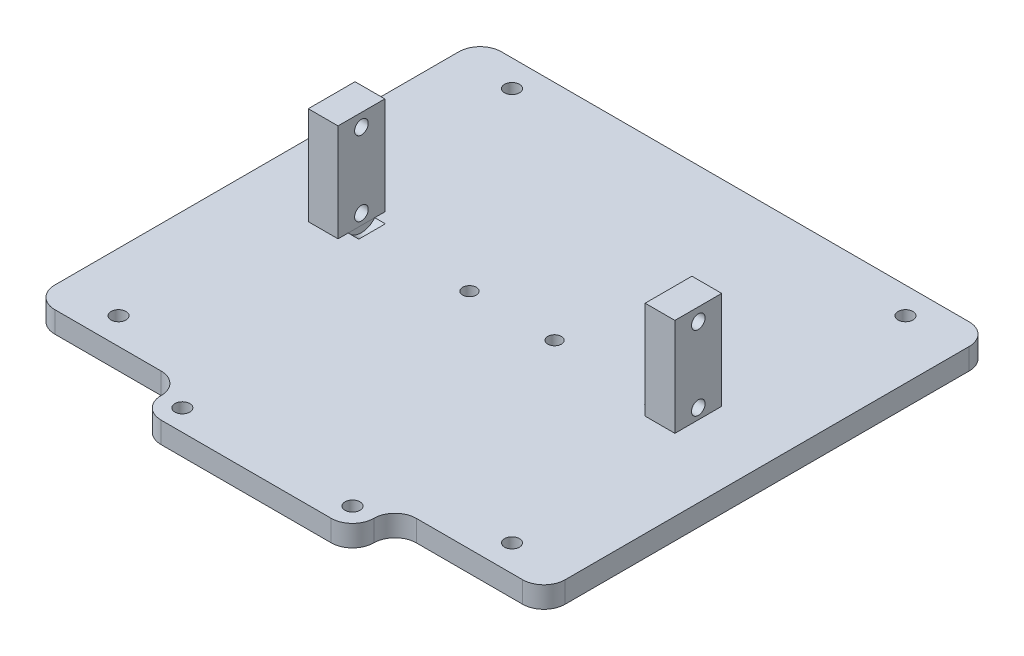
SolidWorks part; units mm, degrees
ref_plane "정면" through (0, 0, 0) normal (0, 0, 1) x (1, 0, 0)
ref_plane "윗면" through (0, 0, 0) normal (0, 1, 0) x (1, 0, 0)
ref_plane "우측면" through (0, 0, 0) normal (1, 0, 0) x (0, 0, -1)
sketch "스케치1" plane through (0, 0, 0) normal (0, 1, 0) x (1, 0, 0)
  line L0 (-25, -52.5) -> (-60, -52.5)
  line L1 (60, 52.5) -> (-60, 52.5)
  line L2 (60, 52.5) -> (60, -52.5)
  line L3 (60, -52.5) -> (25, -52.5)
  line L4 (-60, 52.5) -> (-60, -52.5)
  line L5 (60, 52.5) -> (-60, -52.5) construction
  line L6 (60, -52.5) -> (-60, 52.5) construction
  line L7 (25, -62.5) -> (-25, -62.5)
  line L8 (25, -62.5) -> (25, -52.5)
  line L10 (-25, -62.5) -> (-25, -52.5)
  line L11 (25, -62.5) -> (-25, -52.5) construction
  line L12 (25, -52.5) -> (-25, -62.5) construction
  point P0 (0, 0)
  point P6 (0, -57.5)
  dimension "D1" = 120
  dimension "D2" = 105
  dimension "D3" = 50
  dimension "D4" = 10
extrude "보스-돌출1" add sketch "스케치1" along normal blind 5
fillet "필렛1" radius 5 8 edges at (60, 2.5, -52.5) (60, 2.5, 52.5) (-60, 2.5, -52.5) (-60, 2.5, 52.5) (-25, 2.5, 52.5) (25, 2.5, 52.5) (25, 2.5, 62.5) (-25, 2.5, 62.5)
sketch "스케치2" plane through (0, 5, 0) normal (0, 1, 0) x (1, 0, 0)
  line L0 (-43.1, 29.5) -> (-43.1, -5.3) construction
  line L1 (-36.1, -4.8) -> (-43.1, -4.8)
  line L2 (-36.1, -4.8) -> (-36.1, 6.2)
  line L3 (-36.1, 6.2) -> (-43.1, 6.2)
  line L4 (-43.1, -4.8) -> (-43.1, 6.2)
  line L5 (-61.9, -0.8) -> (-43.1, -0.8) construction
  line L6 (-43.1, 2.2) -> (-61.9, 2.2) construction
  dimension "D1" = 7
  dimension "D2" = 4
  dimension "D3" = 4
extrude "보스-돌출2" add sketch "스케치2" along normal blind 23 separate body
sketch "스케치3" plane through (-36.1, 0, 0) normal (1, 0, 0) x (0, 0, -1)
  circle A0 centre (0.7, 7.5) radius 1.5 construction
  circle A1 centre (0.7, 25) radius 1.5 construction
  circle A2 centre (0.7, 25) radius 1.6
  circle A3 centre (0.7, 7.5) radius 1.6
  circle A4 centre (0.7, 7.5) radius 1.5 construction
  circle A5 centre (0.7, 25) radius 1.5 construction
  dimension "D1" = 3.2
  dimension "D2" = 3.2
extrude "컷-돌출1" cut sketch "스케치3" against normal through all
mirror "대칭 복사1" about plane through (0, 0, 0) normal (1, 0, 0) of bodies 103
sketch "스케치5" plane through (0, 5, 0) normal (0, 1, 0) x (1, 0, 0)
  circle A0 centre (-46.25, -46.25) radius 1.75 construction
  circle A1 centre (-46.25, 46.25) radius 1.75 construction
  circle A2 centre (46.25, 46.25) radius 1.75 construction
  circle A3 centre (46.25, -46.25) radius 1.75 construction
  circle A4 centre (-46.25, -46.25) radius 1.75
  circle A5 centre (-46.25, 46.25) radius 1.75
  circle A6 centre (46.25, 46.25) radius 1.75
  circle A7 centre (46.25, -46.25) radius 1.75
extrude "컷-돌출3" cut sketch "스케치5" against normal through all
sketch "스케치6" plane through (0, 5, 0) normal (0, 1, 0) x (1, 0, 0)
  circle A0 centre (20, -57.5) radius 1.75 construction
  circle A1 centre (-20, -57.5) radius 1.75 construction
  circle A2 centre (20, -57.5) radius 1.75
  circle A3 centre (-20, -57.5) radius 1.75
extrude "컷-돌출4" cut sketch "스케치6" against normal through all
sketch "Sketch2" plane through (36.1, 0, 0) normal (-1, 0, 0) x (0, 0, 1)
  circle A0 centre (-0.7, 7.5) radius 4
  dimension "D1" = 8
extrude "Cut-Extrude1" cut sketch "Sketch2" along normal blind 2.5
sketch "Sketch3" plane through (-36.1, 0, 0) normal (1, 0, 0) x (0, 0, -1)
  circle A0 centre (0.7, 7.5) radius 4
  dimension "D1" = 8
extrude "Cut-Extrude2" cut sketch "Sketch3" along normal blind 2.5
sketch "Sketch4" plane through (0, 5, 0) normal (0, 1, 0) x (1, 0, 0)
  circle A0 centre (10, 0) radius 1.5 construction
  circle A1 centre (-10, 0) radius 1.5 construction
  circle A2 centre (10, 0) radius 1.5 construction
  circle A3 centre (-10, 0) radius 1.5 construction
  circle A4 centre (-10, 0) radius 1.6
  circle A5 centre (10, 0) radius 1.6
  dimension "D1" = 3.2
  dimension "D2" = 3.2
extrude "Cut-Extrude3" cut sketch "Sketch4" against normal through all and the other way through all
